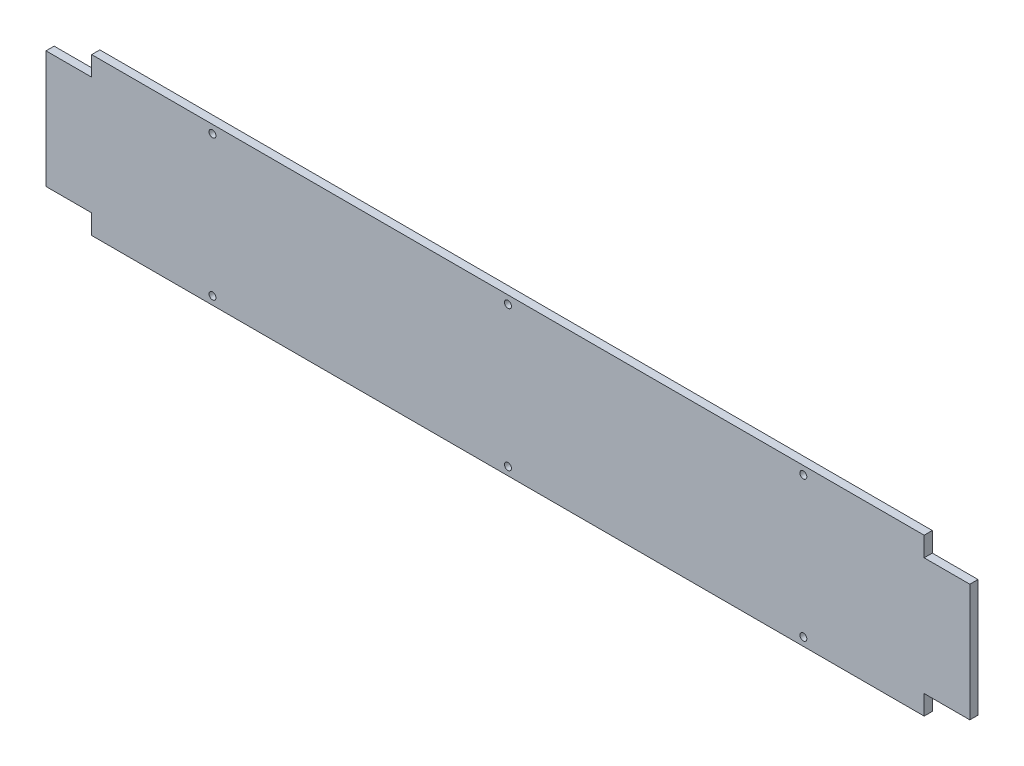
SolidWorks part; units mm, degrees
ref_plane "Front Plane" through (0, 0, 0) normal (0, 0, 1) x (1, 0, 0)
ref_plane "Top Plane" through (0, 0, 0) normal (0, 1, 0) x (1, 0, 0)
ref_plane "Right Plane" through (0, 0, 0) normal (1, 0, 0) x (0, 0, -1)
sketch "Sketch1" plane through (0, 0, 0) normal (0, 0, 1) x (1, 0, 0)
  line L9 (0, 0) -> (510, 0)
  line L10 (0, 0) -> (0, 96)
  line L11 (0, 96) -> (510, 96)
  line L12 (510, 0) -> (510, 96)
  dimension "D1" = 96
  dimension "D2" = 510
extrude "Boss-Extrude1" add sketch "Sketch1" along normal blind 5
sketch "Sketch2" plane through (0, 0, 5) normal (0, 0, 1) x (1, 0, 0)
  line L0 (0, 96) -> (0, 0) construction
  line L3 (510, 96) -> (0, 96) construction
  line L4 (32.0519, 48) -> (507.2554, 48) construction
  circle A0 centre (74, 91) radius 2.125
  circle A1 centre (255, 91) radius 2.125
  circle A2 centre (436, 91) radius 2.125
  circle A3 centre (436, 5) radius 2.125
  circle A4 centre (255, 5) radius 2.125
  circle A5 centre (74, 5) radius 2.125
  dimension "D1" = 4.25
  dimension "D2" = 4.25
  dimension "D3" = 4.25
  dimension "D6" = 181
  dimension "D4" = 74
  dimension "D5" = 181
  dimension "D7" = 5
  dimension "D8" = 48
extrude "Cut-Extrude1" cut sketch "Sketch2" against normal blind 5
sketch "Sketch3" plane through (0, 0, 5) normal (0, 0, 1) x (1, 0, 0)
  line L0 (510, 0) -> (510, 96) construction
  line L1 (510, 84) -> (538, 84)
  line L2 (510, 84) -> (510, 12)
  line L3 (510, 12) -> (538, 12)
  line L4 (538, 84) -> (538, 12)
  line L5 (0, 96) -> (0, 0) construction
  line L6 (0, 84) -> (-28, 84)
  line L7 (0, 84) -> (0, 12)
  line L8 (0, 12) -> (-28, 12)
  line L9 (-28, 84) -> (-28, 12)
  line L10 (510, 96) -> (0, 96) construction
  line L11 (0, 0) -> (510, 0) construction
  dimension "D1" = 12
  dimension "D2" = 28
  dimension "D3" = 12
  dimension "D4" = 12
  dimension "D5" = 12
  dimension "D6" = 28
extrude "Boss-Extrude2" add sketch "Sketch3" against normal blind 5
